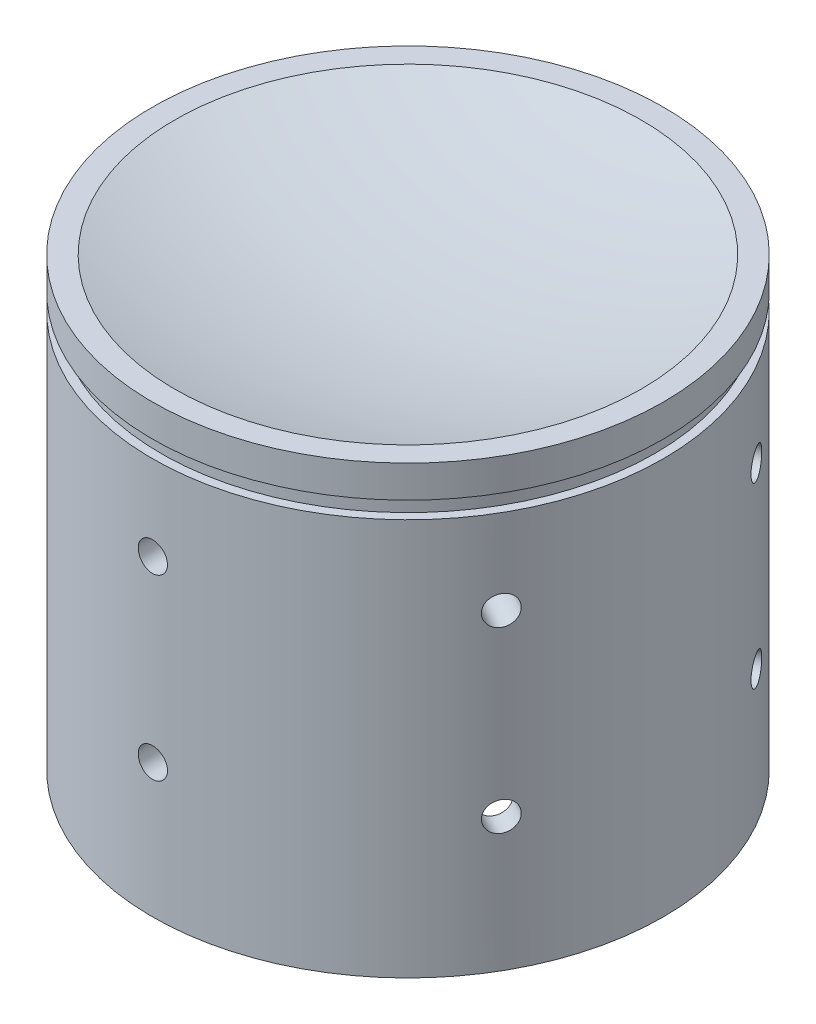
SolidWorks part; units mm, degrees
note: '?' marks a value the reader was unsure of.
material "6061-T6 (SS)"
ref_plane "Front Plane" through (0, 0, 0) normal (0, 0, 1) x (1, 0, 0)
ref_plane "Top Plane" through (0, 0, 0) normal (0, 1, 0) x (1, 0, 0)
ref_plane "Right Plane" through (0, 0, 0) normal (1, 0, 0) x (0, 0, -1)
sketch "Sketch1" plane through (0, 0, 0) normal (0, 0, 1) x (1, 0, 0)
  line L0 (0, -25.4) -> (36.4236, -25.4)
  line L1 (0, 0) -> (36.4236, 0)
  line L2 (0, 0) -> (0, -63.5)
  line L3 (0, -63.5) -> (36.4236, -63.5)
  line L4 (36.4236, 0) -> (36.4236, -63.5)
  line L5 (36.3855, -25.4) -> (36.3855, 0)
  line L6 (0, -14.4216) -> (0, 22.2823) construction
  line L7 (33.2105, 0) -> (33.2105, -25.4)
  line L8 (36.3855, -25.4) -> (36.3855, -63.5)
  line L9 (0, 0) -> (0, -5.08)
  line L10 (0, -5.08) -> (0, -10.16)
  line L11 (0, -10.16) -> (36.3855, -10.16)
  line L12 (36.3855, -10.16) -> (36.3855, 0)
  line L13 (33.2105, -25.4) -> (33.2105, -63.5)
  line L14 (36.3855, -4.572) -> (35.1409, -4.572)
  line L15 (36.3855, -4.572) -> (36.3855, -6.985)
  line L16 (36.3855, -6.985) -> (35.1409, -6.985)
  line L17 (35.1409, -4.572) -> (35.1409, -6.985)
  arc A0 (0, -5.08) -> (33.2105, 0) centre (0, 106.0168) ccw
  point P22 (35.7632, -6.985)
  dimension "D8" = 5.08
  dimension "D1" = 36.4236
  dimension "D2" = 63.5
  dimension "D3" = 25.4
  dimension "D5" = 3.175
  dimension "D6" = 4.572
  dimension "D7" = 5.08
  dimension "D9" = 1.2446
  dimension "D10" = 2.413
ref_axis "Axis1" through (0, 0, 0) along (0, -1, 0)?
revolve "Revolve2" add sketch "Sketch1" angle 360 about L2
hole_wizard "#19 (0.164) Diameter Hole1" positions "3DSketch7" profile "Sketch8" hole size "#19" standard "ANSI Inch" end condition through all
sketch3d "3DSketch7"
  point P3 (0, -19.05, 36.3855)
  point P14 (0, -44.45, 36.3855)
sketch "Sketch8" plane through (0, -19.05, 36.3855) normal (1, 0, 0) x (0, -1, 0)
  line L0 (0, 0) -> (0, 72.771)
  line L1 (0, 72.771) -> (2.0828, 72.771)
  line L2 (2.0828, 72.771) -> (2.0828, 0)
  line L5 (2.0828, 0) -> (0, 0)
  line L11 (0, -6.35) -> (0, 107.95) construction
  dimension "Thru Hole Dia." = 4.1656
  dimension "Thru Hole Depth" = 72.771
pattern_circular "CirPattern2" count 6 every 60 about axis through (0, 0, 0) along (0, -1, 0) of "#19 (0.164) Diameter Hole1"
